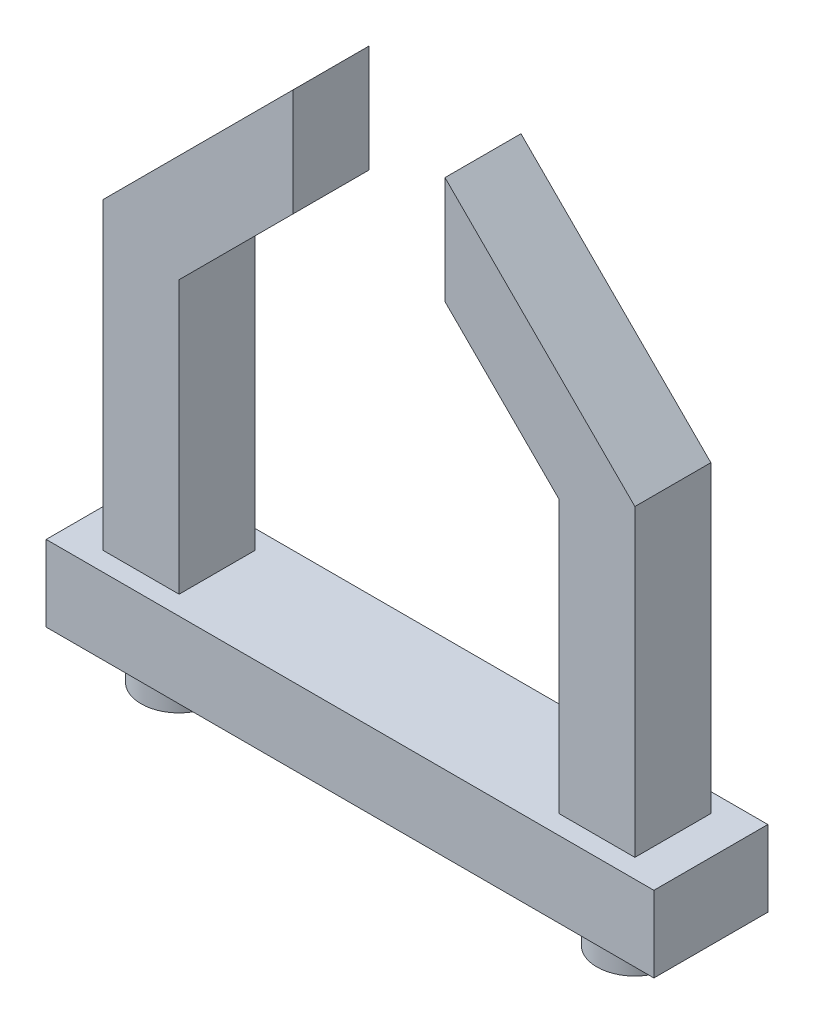
SolidWorks part; units mm, degrees
material "ABS"
ref_plane "FRONT" through (0, 0, 0) normal (0, 0, 1) x (1, 0, 0)
ref_plane "TOP" through (0, 0, 0) normal (0, 1, 0) x (1, 0, 0)
ref_plane "RIGHT" through (0, 0, 0) normal (1, 0, 0) x (0, 0, -1)
ref_axis "Axis1" through (-80.9, 0, 0) along (1, 0, 0)
ref_axis "Axis2" through (0, 0, -80.9) along (0, 0, 1)
ref_axis "Axis3" through (0, 50, 0) along (0, -1, 0)
sketch "Sketch1" plane through (0, 0, 0) normal (0, 0, 1) x (1, 0, 0)
  line L0 (-20, 0) -> (0, 0)
  line L2 (-17.5, 25) -> (-5, 37.5)
  line L3 (-5, 37.5) -> (-5, 30.4289)
  line L4 (-5, 30.4289) -> (-12.5, 22.9289)
  line L5 (-12.5, 22.9289) -> (-12.5, 5)
  line L6 (-12.5, 5) -> (0, 5)
  line L7 (0, 0) -> (0, 5)
  line L8 (-12.5, 5) -> (-17.5, 5)
  line L9 (-17.5, 25) -> (-17.5, 5)
  line L10 (-17.5, 5) -> (-20, 5)
  line L11 (-20, 5) -> (-20, 0)
  point P2 (-19.8591, 0)
  point P4 (0, 0)
  point P13 (-18.8724, 0)
  dimension "D1" = 20
  dimension "D2" = 5
  dimension "D3" = 17.5
  dimension "D4" = 5
  dimension "D5" = 5
  dimension "D6" = 135
  dimension "D7" = 5
  dimension "D8" = 25
extrude "Boss-Extrude1" add sketch "Sketch1" along normal mid plane 5 contours L8 L5 L4 L3 L2 region at (-12.9347, 20.7554, 0)
extrude "Boss-Extrude2" add sketch "Sketch1<3>" along normal mid plane 7.5 contours L6 L8 L0 L7 region at (-10, 2.5, 0)
sketch "Sketch1<3>" plane through (0, 0, 0) normal (0, 0, 1) x (1, 0, 0) same geometry as "Sketch1"
sketch "Sketch3" plane through (0, 0, 0) normal (0, -1, 0) x (1, 0, 0)
  line L0 (0, 0) -> (-15, 0) construction
  circle A0 centre (-15, 0) radius 2.5
  point P3 (-15.056, 0)
  point P7 (-17.5, 0)
  dimension "D1" = 5
  dimension "D2" = 15
extrude "Boss-Extrude3" add sketch "Sketch3" along direction (0, 1, 0) on the side of the normal blind 2.5
mirror "Mirror1" about plane through (0, 0, 0) normal (1, 0, 0) of "Boss-Extrude3", "Boss-Extrude2", "Boss-Extrude1"
